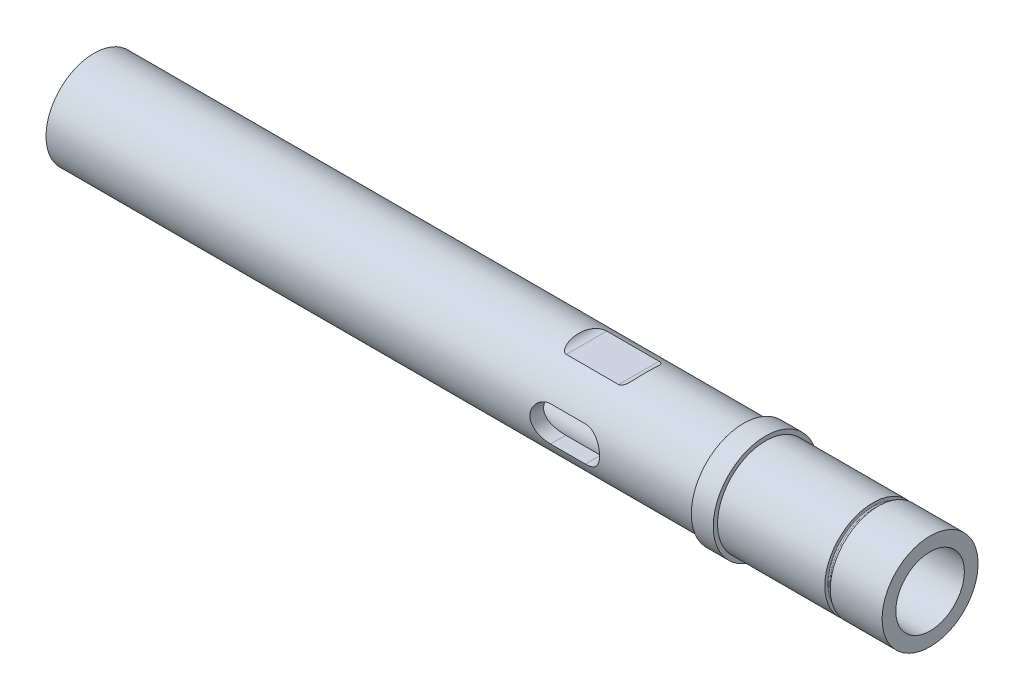
SolidWorks part; units mm, degrees
material "AISI 304"
ref_plane "Frontal Plane" through (0, 0, 0) normal (0, 0, 1) x (1, 0, 0)
ref_plane "Horizontal Plane" through (0, 0, 0) normal (0, 1, 0) x (1, 0, 0)
ref_plane "Profile Plane" through (0, 0, 0) normal (1, 0, 0) x (0, 0, -1)
sketch "Sketch1" plane through (0, 0, 0) normal (1, 0, 0) x (0, 0, -1)
  circle A0 centre (0, 0) radius 17.5
  circle A1 centre (0, 0) radius 12.5
  dimension "D1" = 35
  dimension "D2" = 25
extrude "Boss-Extrude1" add sketch "Sketch1" along normal mid plane 304.8
ref_plane "Plane1" through (92.4, 0, 0) normal (-1, 0, 0) x (0, 0, 1)
sketch "Sketch2" plane through (92.4, 0, 0) normal (-1, 0, 0) x (0, 0, 1)
  circle A0 centre (0, 0) radius 19.05
  circle A1 centre (0, 0) radius 17.5
  dimension "D1" = 38.1
  dimension "D2" = 35
extrude "Boss-Extrude2" add sketch "Sketch2" along normal blind 8
ref_plane "Plane2" through (133.52, 0, 0) normal (1, 0, 0) x (0, 0, -1)
sketch "Sketch4" plane through (133.52, 0, 0) normal (1, 0, 0) x (0, 0, -1)
  circle A0 centre (0, 0) radius 17.5
  circle A1 centre (0, 0) radius 16
  dimension "D1" = 35
  dimension "D2" = 32
extrude "Cut-Extrude2" cut sketch "Sketch4" against normal blind 2
fillet "Fillet1" radius 0.4064 2 edges at (133.52, 0, -16) (131.52, 0, -16)
sketch "Sketch8" plane through (0, 0, 0) normal (0, 0, 1) x (1, 0, 0)
  line L6 (84.4, 17.5) -> (84.4, -17.5) construction
  line L7 (0, 0) -> (84.4, 0) construction
  line L8 (24, 19.05) -> (49.4, 19.05)
  line L9 (24, 19.05) -> (24, 15.875)
  line L10 (24, 15.875) -> (49.4, 15.875)
  line L11 (49.4, 19.05) -> (49.4, 15.875)
  line L12 (24, 19.05) -> (49.4, 15.875) construction
  line L13 (24, 15.875) -> (49.4, 19.05) construction
  line L14 (84.4, 19.05) -> (84.4, -19.05) construction
  line L15 (24, -15.875) -> (49.4, -15.875)
  line L16 (49.4, -19.05) -> (49.4, -15.875)
  line L17 (24, -19.05) -> (49.4, -19.05)
  line L18 (24, -19.05) -> (24, -15.875)
  point P6 (36.7, 17.4625)
  dimension "D1" = 25.4
  dimension "D2" = 35
  dimension "D3" = 3.175
  dimension "D4" = 15.875
extrude "Cut-Extrude3" cut sketch "Sketch8" against normal through all both and the other way through all
fillet "Fillet2" radius 3.175 4 edges at (49.4, -15.875, 0) (24, -15.875, 0) (49.4, 15.875, 0) (24, 15.875, 0)
sketch "Sketch9" plane through (0, 0, 0) normal (0, 0, 1) x (1, 0, 0)
  line L0 (36.7, 14.0824) -> (36.7, -14.0824) construction
  line L4 (43.05, 0) -> (30.35, 0) construction
  line L5 (43.05, -6.35) -> (30.35, -6.35)
  line L6 (43.05, 6.35) -> (30.35, 6.35)
  line L7 (0, 0) -> (84.4, 0) construction
  line L8 (84.4, 19.05) -> (84.4, -19.05) construction
  line L9 (46.225, 15.875) -> (27.175, 15.875) construction
  arc A1 (43.05, -6.35) -> (43.05, 6.35) centre (43.05, 0) ccw
  arc A2 (30.35, 6.35) -> (30.35, -6.35) centre (30.35, 0) ccw
  point P8 (36.7, 15.875)
  point P11 (36.7, 0)
  point P18 (0, 0)
  dimension "D1" = 6.35
  dimension "D3" = 6.35
  dimension "D2" = 12.7
  dimension "D4" = 12.7
extrude "Cut-Extrude4" cut sketch "Sketch9" along normal up to next
